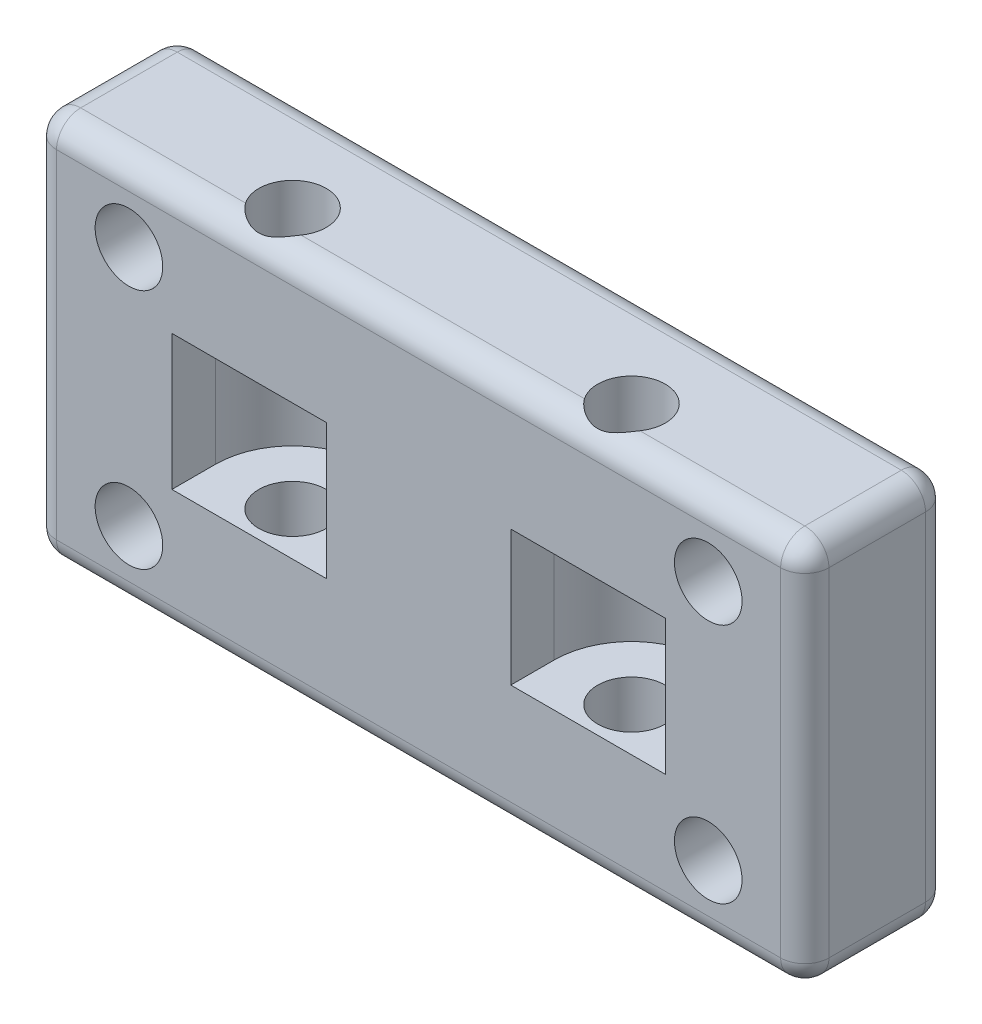
SolidWorks part; units mm, degrees
ref_plane "Front Plane" through (0, 0, 0) normal (0, 0, 1) x (1, 0, 0)
ref_plane "Top Plane" through (0, 0, 0) normal (0, 1, 0) x (1, 0, 0)
ref_plane "Right Plane" through (0, 0, 0) normal (1, 0, 0) x (0, 0, -1)
sketch "Sketch1" plane through (0, 0, 0) normal (0, 0, 1) x (1, 0, 0)
  line L2 (-25.4, -12.7) -> (-25.4, 12.7)
  line L3 (-25.4, 12.7) -> (25.4, 12.7)
  line L10 (25.4, -12.7) -> (25.4, 12.7)
  line L11 (-25.4, -12.7) -> (25.4, -12.7)
  line L14 (-25.4, 12.7) -> (25.4, -12.7) construction
  point P2 (0, 0)
  dimension "D1" = 50.8
  dimension "D2" = 25.4
extrude "Boss-Extrude1" add sketch "Sketch1" along normal blind 9.525
sketch "Sketch4" plane through (0, 0, 0) normal (0, 1, 0) x (1, 0, 0)
  line L7 (25.4, -9.525) -> (-25.4, -9.525) construction
  line L8 (-16.2242, -6.6675) -> (-16.2242, -9.525)
  line L9 (-6.0642, -6.6675) -> (-6.0643, -9.525)
  line L10 (-6.0643, -9.525) -> (-16.2242, -9.525)
  line L11 (-25.4, -9.525) -> (-25.4, 0) construction
  arc A2 (-6.0642, -6.6675) -> (-16.2242, -6.6675) centre (-11.1442, -6.6675) ccw
  dimension "D1" = 10.16
  dimension "D2" = 2.8575
  dimension "D3" = 14.2558
extrude "Cut-Extrude2" cut sketch "Sketch4" against normal mid plane 8.89
ref_plane "Plane3" through (0, 0, 0) normal (-1, 0, 0) x (0, 0, 1)
sketch "Sketch2" plane through (0, 0, 9.525) normal (0, 0, 1) x (1, 0, 0)
  line L0 (-25.4, -12.7) -> (25.4, -12.7) construction
  line L1 (-25.4, 12.7) -> (-25.4, -12.7) construction
  circle A0 centre (-19.05, 7.9375) radius 2.2225
  dimension "D1" = 4.445
  dimension "D2" = 20.6375
  dimension "D3" = 6.35
extrude "Cut-Extrude1" cut sketch "Sketch2" against normal up to surface (9.525 mm away) up to face at (0, 0, 0)
sketch "Sketch5" plane through (0, 12.7, 0) normal (0, 1, 0) x (1, 0, 0)
  line L0 (25.4, -9.525) -> (-25.4, -9.525) construction
  line L1 (-25.4, -9.525) -> (-25.4, 0) construction
  circle A0 centre (-11.1442, -6.6675) radius 2.2225
  dimension "D3" = 4.445
  dimension "D1" = 2.8575
  dimension "D2" = 14.2558
extrude "Cut-Extrude3" cut sketch "Sketch5" along normal blind 3.175 and the other way through all
mirror "Mirror1" about plane through (0, 0, 0) normal (0, 1, 0) of "Cut-Extrude1"
mirror "Mirror2" about plane through (0, 0, 0) normal (-1, 0, 0) of "Mirror1", "Cut-Extrude3", "Cut-Extrude2"
fillet "Fillet1" radius 1.5875 12 edges at (-25.4, 12.7, 4.7625) (-25.4, 0, 9.525) (-25.4, -12.7, 4.7625) (-25.4, 0, 0) (25.4, -12.7, 4.7625) (25.4, 0, 9.525) (25.4, 12.7, 4.7625) (25.4, 0, 0) (0, -12.7, 0) (0, -12.7, 9.525) (0, 12.7, 9.525) (0, 12.7, 0)
